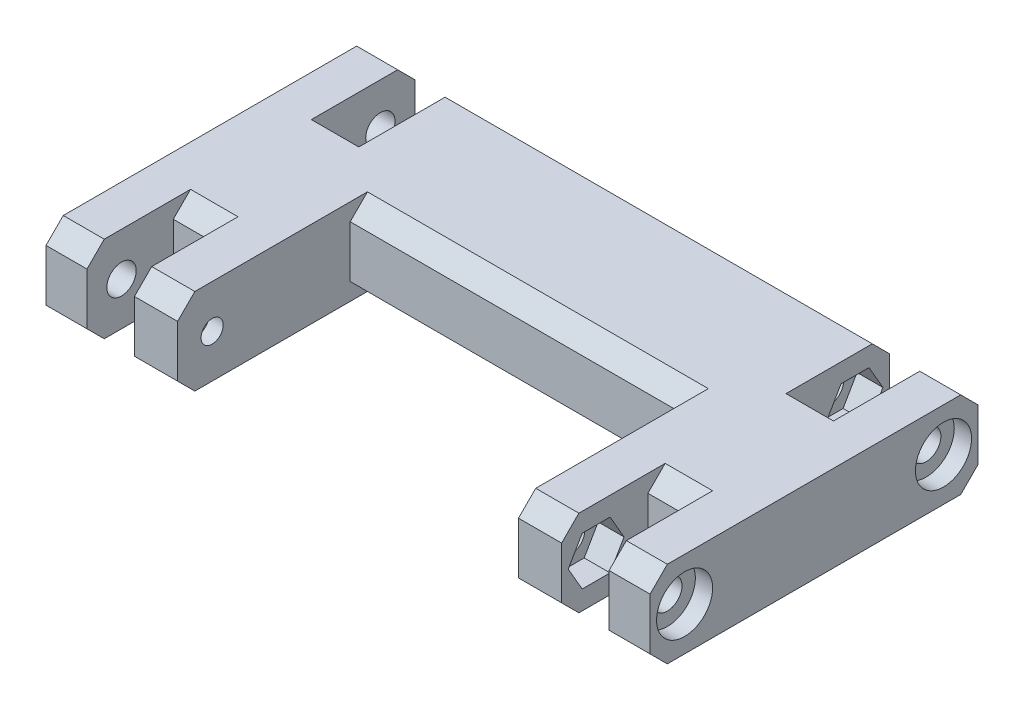
SolidWorks part; units mm, degrees
ref_plane "Front Plane" through (0, 0, 0) normal (0, 0, 1) x (1, 0, 0)
ref_plane "Top Plane" through (0, 0, 0) normal (0, 1, 0) x (1, 0, 0)
ref_plane "Right Plane" through (0, 0, 0) normal (1, 0, 0) x (0, 0, -1)
sketch "Sketch1" plane through (0, 0, 0) normal (0, 1, 0) x (1, 0, 0)
  line L1 (-35, -19) -> (35, -19)
  line L2 (-35, -19) -> (-35, 19)
  line L3 (-35, 19) -> (35, 19)
  line L4 (35, -19) -> (35, 19)
  line L5 (-35, -19) -> (35, 19) construction
  line L6 (-35, 19) -> (35, -19) construction
  point P0 (0, 0)
  dimension "D1" = 70
  dimension "D2" = 38
extrude "Boss-Extrude1" add sketch "Sketch1" along normal blind 10
sketch "Sketch2" plane through (0, 10, 0) normal (0, 1, 0) x (1, 0, 0)
  line L0 (35, 19) -> (-35, 19) construction
  line L1 (-30.25, 19) -> (-24.75, 19)
  line L2 (-30.25, 19) -> (-30.25, 9)
  line L3 (-30.25, 9) -> (-24.75, 9)
  line L4 (-24.75, 19) -> (-24.75, 9)
  line L5 (0, 0) -> (0, 19) construction
  line L6 (24.75, 19) -> (24.75, 9)
  line L7 (30.25, 9) -> (24.75, 9)
  line L8 (30.25, 19) -> (30.25, 9)
  line L9 (30.25, 19) -> (24.75, 19)
  dimension "D1" = 5.5
  dimension "D2" = 10
  dimension "D3" = 49.5
extrude "Cut-Extrude1" cut sketch "Sketch2" against normal through all
hole_wizard "CBORE for M3 Cheese Head Screw1" positions "Sketch7" profile "Sketch8" counterbore size "M3" standard "ISO"
sketch "Sketch7" plane through (35, 0, 0) normal (1, 0, 0) x (0, 0, -1)
  line L0 (-19, 10) -> (19, 10) construction
  line L1 (19, 10) -> (19, 0) construction
  point P0 (15, 5)
  dimension "D1" = 5
  dimension "D2" = 4
sketch "Sketch8" plane through (35, 5, -15) normal (0, 1, 0) x (0, 0, -1)
  line L0 (0, 0) -> (0, 16.0215)
  line L1 (0, 16.0215) -> (1.7, 15)
  line L2 (1.7, 15) -> (1.7, 2)
  line L3 (1.7, 2) -> (3.25, 2)
  line L4 (3.25, 2) -> (3.25, 0)
  line L5 (3.25, 0) -> (0, 0)
  line L10 (0, 16.0215) -> (-1.7, 15) construction
  line L11 (0, -6.35) -> (0, 107.95) construction
  dimension "Hole Dia." = 3.4
  dimension "Hole Depth" = 15
  dimension "C'Bore Dia." = 6.5
  dimension "C'Bore Depth" = 2
  dimension "Drill Angle" = 118
sketch "Sketch9" plane through (24.75, 0, 0) normal (1, 0, 0) x (0, 0, -1)
  line L1 (16.6166, 7.8) -> (13.3834, 7.8)
  line L2 (13.3834, 7.8) -> (11.7668, 5)
  line L3 (11.7668, 5) -> (13.3834, 2.2)
  line L4 (13.3834, 2.2) -> (16.6166, 2.2)
  line L5 (16.6166, 2.2) -> (18.2332, 5)
  line L6 (18.2332, 5) -> (16.6166, 7.8)
  circle A0 centre (15, 5) radius 2.8 construction
  dimension "D1" = 5.6
extrude "Cut-Extrude2" cut sketch "Sketch9" against normal blind 3
mirror "Mirror1" about plane through (0, 0, 0) normal (1, 0, 0) of "Cut-Extrude2", "CBORE for M3 Cheese Head Screw1"
mirror "Mirror2" about plane through (0, 0, 0) normal (0, 0, 1) of "Cut-Extrude1", "CBORE for M3 Cheese Head Screw1", "Cut-Extrude2", "Mirror1"
chamfer "Chamfer1" distance 2 angle 45 12 edges at (32.625, 0, -19) (32.625, 10, -19) (0, 0, -19) (0, 10, -19) (-32.625, 0, -19) (-32.625, 10, -19) (-32.625, 0, 19) (32.625, 0, 19) (0, 0, 19) (32.625, 10, 19) (-32.625, 10, 19) (0, 10, 19)
sketch "Sketch10" plane through (0, 10, 0) normal (0, 1, 0) x (1, 0, 0)
  line L0 (0, 0) -> (0, -19) construction
  line L1 (24.75, -19) -> (-24.75, -19) construction
  line L2 (-24.75, -9) -> (-24.75, -17) construction
  line L3 (-19.75, -19) -> (19.75, -19)
  line L4 (-19.75, -19) -> (-19.75, 1)
  line L5 (-19.75, 1) -> (19.75, 1)
  line L6 (19.75, -19) -> (19.75, 1)
  line L7 (-19.75, -19) -> (19.75, 1) construction
  line L8 (-19.75, 1) -> (19.75, -19) construction
  point P5 (0, -9)
  dimension "D1" = 5
  dimension "D2" = 20
extrude "Cut-Extrude3" cut sketch "Sketch10" against normal through all
chamfer "Chamfer2" distance 2 angle 45 2 edges at (0, 0, -1) (0, 10, -1)
chamfer "Chamfer3" distance 2 angle 45 8 edges at (27.5, 0, -9) (27.5, 10, -9) (27.5, 10, 9) (27.5, 0, 9) (-27.5, 10, 9) (-27.5, 0, 9) (-27.5, 0, -9) (-27.5, 10, -9)
